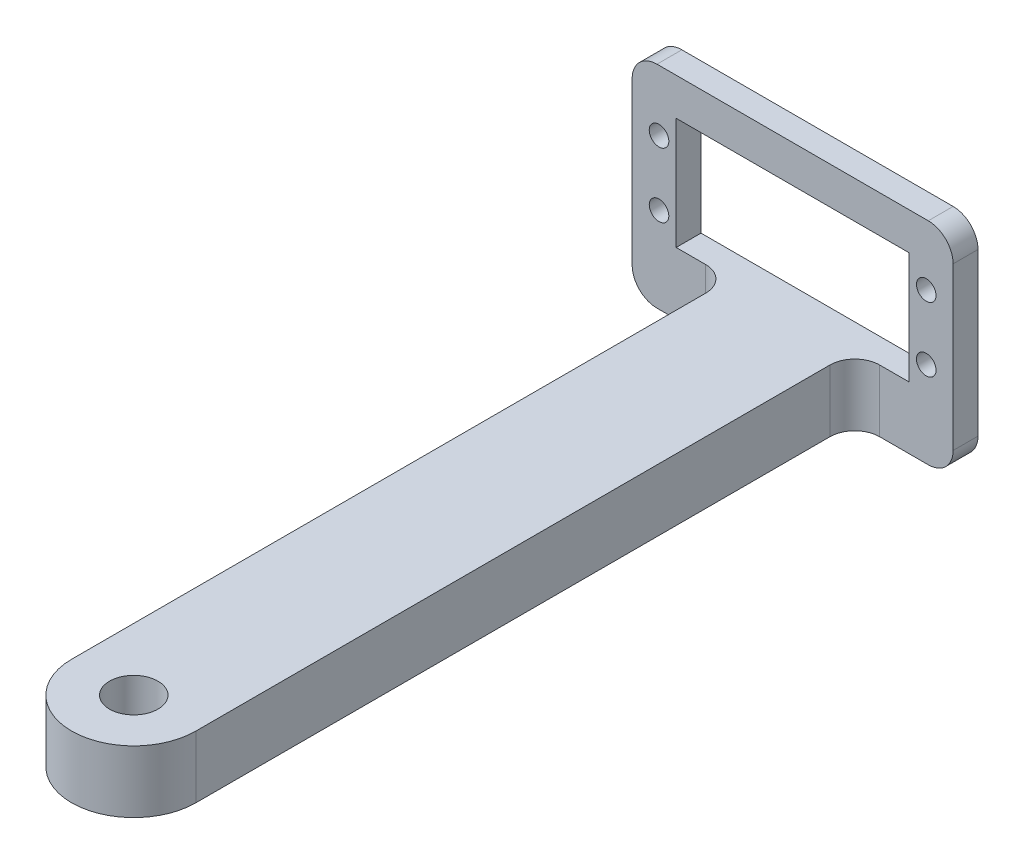
SolidWorks part; units mm, degrees
ref_plane "Front Plane" through (0, 0, 0) normal (0, 0, 1) x (1, 0, 0)
ref_plane "Top Plane" through (0, 0, 0) normal (0, 1, 0) x (1, 0, 0)
ref_plane "Right Plane" through (0, 0, 0) normal (1, 0, 0) x (0, 0, -1)
sketch "Sketch1" plane through (0, 0, 0) normal (0, 0, 1) x (1, 0, 0)
  line L1 (-6.35, 3.175) -> (6.35, 3.175)
  line L2 (-6.35, 3.175) -> (-6.35, -3.175)
  line L3 (-6.35, -3.175) -> (6.35, -3.175)
  line L4 (6.35, 3.175) -> (6.35, -3.175)
  point P4 (0, 3.175)
  point P6 (6.35, 0)
  dimension "D1" = 12.7
  dimension "D2" = 6.35
extrude "Boss-Extrude1" add sketch "Sketch1" along normal mid plane 76.2
sketch "Sketch2" plane through (0, 3.175, 0) normal (0, 1, 0) x (1, 0, 0)
  line L0 (6.35, -38.1) -> (6.35, 38.1) construction
  line L1 (6.35, -38.1) -> (-6.35, -38.1) construction
  circle A0 centre (0, -31.75) radius 2.4765
  dimension "D1" = 4.953
  dimension "D2" = 6.35
  dimension "D3" = 6.35
extrude "Cut-Extrude1" cut sketch "Sketch2" against normal up to next
fillet "Fillet1" 2 edges at (-6.35, 0, 38.1) (6.35, 0, 38.1) type full round first side face at (-6.35, 0, 0) second side face at (6.35, 0, 0) middle face at (0, 0, 38.1)
sketch "Sketch3" plane through (0, 0, -38.1) normal (0, 0, -1) x (-1, 0, 0)
  line L0 (6.35, -3.175) -> (-6.35, -3.175) construction
  line L1 (-16.3957, 18.415) -> (16.3957, 18.415)
  line L2 (-16.3957, 18.415) -> (-16.3957, -3.175)
  line L3 (-16.3957, -3.175) -> (16.3957, -3.175)
  line L4 (16.3957, 18.415) -> (16.3957, -3.175)
  line L5 (-11.8999, 3.925) -> (-11.8999, 13.855) construction
  line L6 (-16.3957, 13.855) -> (-16.3957, 3.925) construction
  line L7 (16.3957, 13.855) -> (16.3957, 3.925) construction
  line L8 (3.9889, 3.175) -> (-11.1499, 3.175) construction
  line L9 (11.8999, 8.89) -> (11.8999, 13.855) construction
  line L10 (-11.8999, 3.175) -> (-11.8999, 14.605)
  line L11 (11.8999, 3.175) -> (-11.8999, 3.175)
  line L12 (11.8999, 3.175) -> (11.8999, 14.605)
  line L13 (11.8999, 14.605) -> (-11.8999, 14.605)
  line L14 (-15.6457, 14.605) -> (-11.1499, 14.605) construction
  line L15 (11.1499, 3.175) -> (15.6457, 3.175) construction
  line L33 (3.9889, 14.605) -> (-11.1499, 14.605) construction
  circle A38 centre (13.65, 5.588) radius 1 construction
  circle A39 centre (13.65, 12.192) radius 1 construction
  circle A40 centre (-13.65, 5.588) radius 1 construction
  circle A41 centre (-13.65, 12.192) radius 1 construction
  circle A42 centre (13.65, 5.588) radius 1
  circle A43 centre (13.65, 12.192) radius 1
  circle A44 centre (-13.65, 5.588) radius 1
  circle A45 centre (-13.65, 12.192) radius 1
  point P7 (11.8999, 14.605)
  point P13 (0, 0)
  point P15 (-8.5513, -6.7122)
  point P29 (11.699, 3.175)
  point P31 (11.8999, 3.925)
  point P32 (-11.8999, 14.605)
  point P36 (-11.7598, 14.605)
  point P39 (11.8999, 14.4779)
  point P42 (11.8999, 3.175)
  point P45 (-11.8999, 3.175)
  point P47 (0, 0)
  dimension "D1" = 3.81
extrude "Boss-Extrude2" add sketch "Sketch3" against normal blind 2.54
fillet "Fillet3" radius 2.54 6 edges at (-16.3957, 18.415, -36.83) (16.3957, 18.415, -36.83) (16.3957, -3.175, -36.83) (6.35, 0, -35.56) (-6.35, 0, -35.56) (-16.3957, -3.175, -36.83)
